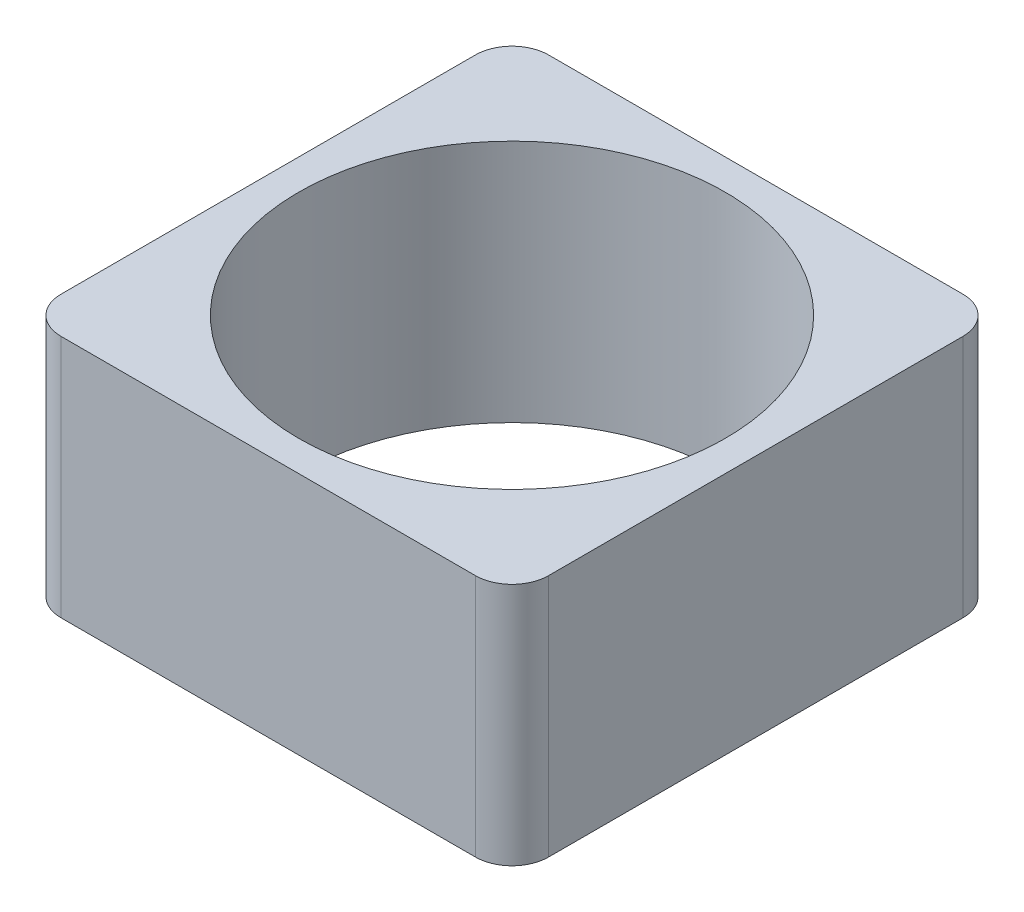
SolidWorks part; units mm, degrees
ref_plane "Front" through (0, 0, 0) normal (0, 0, 1) x (1, 0, 0)
ref_plane "Top" through (0, 0, 0) normal (0, 1, 0) x (1, 0, 0)
ref_plane "Right" through (0, 0, 0) normal (1, 0, 0) x (0, 0, -1)
sketch "Sketch1" plane through (0, 0, 0) normal (0, 1, 0) x (1, 0, 0)
  line L1 (-20, -20) -> (20, -20)
  line L2 (-20, -20) -> (-20, 20)
  line L3 (-20, 20) -> (20, 20)
  line L4 (20, -20) -> (20, 20)
  line L5 (-20, -20) -> (20, 20) construction
  line L6 (-20, 20) -> (20, -20) construction
  point P0 (0, 0)
  dimension "D1" = 40
extrude "Boss-Extrude1" add sketch "Sketch1" along normal blind 20
fillet "Fillet1" radius 3 4 edges at (-20, 10, -20) (-20, 10, 20) (20, 10, -20) (20, 10, 20)
sketch "Sketch2" plane through (0, 20, 0) normal (0, 1, 0) x (1, 0, 0)
  circle A0 centre (0, 0) radius 17.5
  dimension "D1" = 35
extrude "Cut-Extrude1" cut sketch "Sketch2" against normal through all
